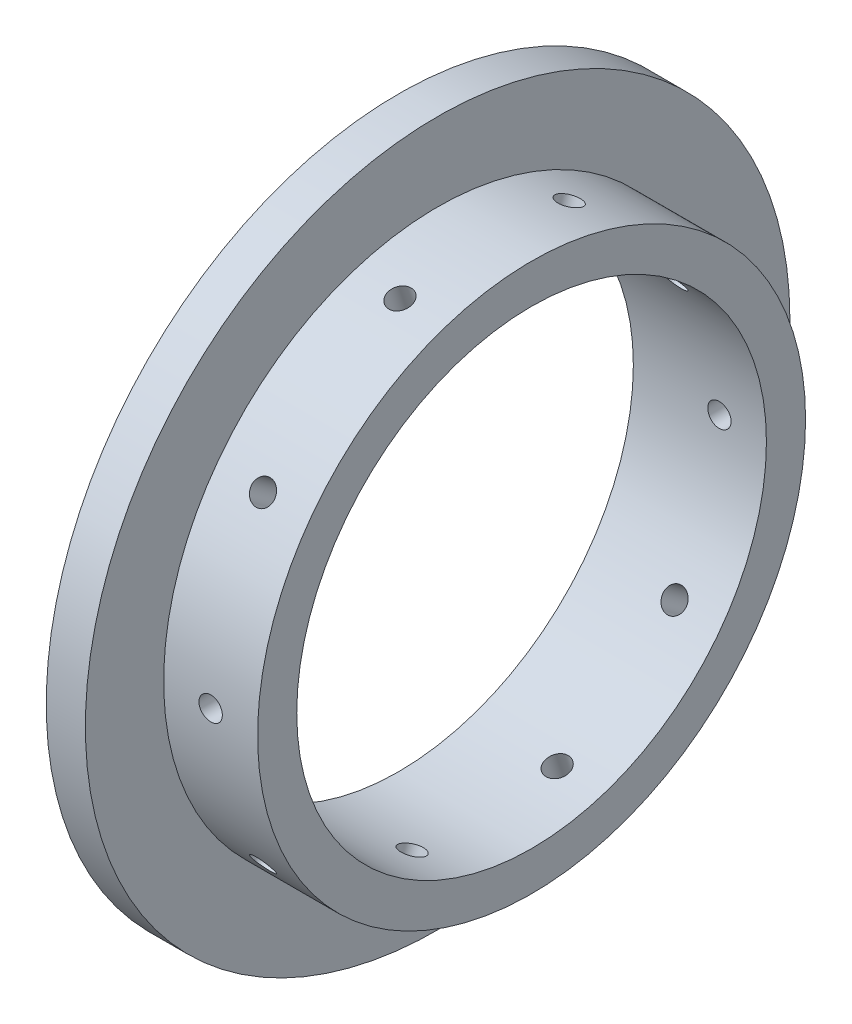
SolidWorks part; units mm, degrees
material "Alloy Steel"
ref_plane "Front Plane" through (0, 0, 0) normal (0, 0, 1) x (1, 0, 0)
ref_plane "Top Plane" through (0, 0, 0) normal (0, 1, 0) x (1, 0, 0)
ref_plane "Right Plane" through (0, 0, 0) normal (1, 0, 0) x (0, 0, -1)
sketch "Sketch1" plane through (0, 0, 0) normal (1, 0, 0) x (0, 0, -1)
  circle A0 centre (0, 0) radius 38.1
  circle A1 centre (0, 0) radius 57.15
  dimension "D1" = 76.2
  dimension "D2" = 114.3
extrude "Boss-Extrude1" add sketch "Sketch1" along normal blind 6.35
sketch "Sketch2" plane through (6.35, 0, 0) normal (1, 0, 0) x (0, 0, -1)
  circle A0 centre (0, 0) radius 44.45
  circle A1 centre (0, 0) radius 38.1
  dimension "D1" = 88.9
  dimension "D2" = 76.2
extrude "Boss-Extrude2" add sketch "Sketch2" along normal blind 15.24
sketch "Sketch3" plane through (0, 0, 0) normal (0, 1, 0) x (1, 0, 0)
  line L0 (0, 0) -> (88.5884, 0) construction
  line L1 (-13.97, 0) -> (13.97, 0) construction
  line L2 (0, 0) -> (0, 82.8947) construction
ref_plane "Plane1" through (0, 0, -44.45) normal (0, 0, -1) x (-1, 0, 0)
sketch "Sketch4" plane through (0, 0, -44.45) normal (0, 0, -1) x (-1, 0, 0)
  line L0 (0, 0) -> (-88.5884, 0) construction
  line L2 (-6.35, 44.45) -> (-6.35, -44.45) construction
  circle A0 centre (-13.97, 0) radius 1.8986
  dimension "D2" = 3.7973
  dimension "D1" = 7.62
extrude "Cut-Extrude1" cut sketch "Sketch4" against normal blind 7.62
pattern_circular "CirPattern1" count 10 over 360 about axis through (0, 0, 0) along (1, 0, 0) of "Cut-Extrude1"
